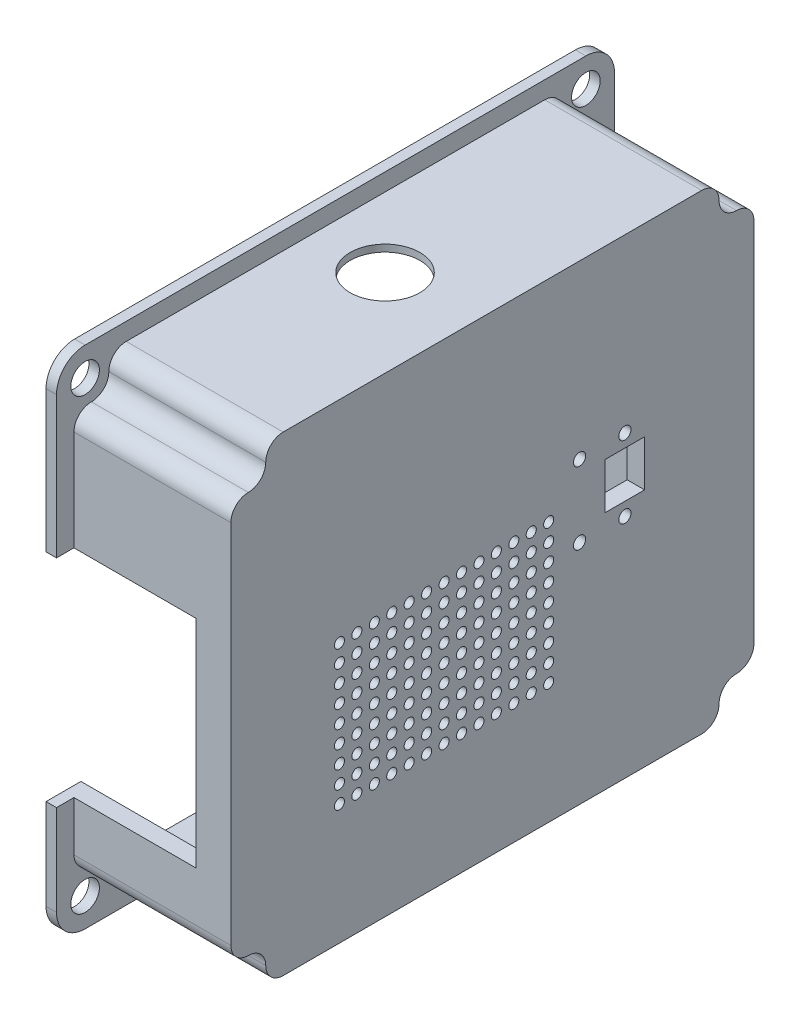
SolidWorks part; units mm, degrees
ref_plane "Alzado" through (0, 0, 0) normal (1, 0, 0) x (0, 1, 0)
ref_plane "Planta" through (0, 0, 0) normal (0, 0, 1) x (0, 1, 0)
ref_plane "Vista lateral" through (0, 0, 0) normal (0, 1, 0) x (-1, 0, 0)
sketch "Croquis2" plane through (0, 0, 0) normal (1, 0, 0) x (0, 1, 0)
  line L0 (72.5, 80) -> (57.5, 80) construction
  line L3 (-64.3, 80) -> (64.3, 80)
  line L4 (72.5, -71.8) -> (72.5, 71.8)
  line L6 (-72.5, 80) -> (-72.5, 65) construction
  line L11 (72.5, 80) -> (72.5, 65) construction
  line L12 (57.5, 75) -> (57.5, 65)
  line L13 (57.5, 65) -> (67.5, 65)
  line L14 (0, 0) -> (0, 80) construction
  line L15 (67.5, 65) -> (67.5, -65)
  line L16 (0, 0) -> (72.5, 0) construction
  line L17 (-57.5, 75) -> (57.5, 75)
  line L18 (-72.5, 80) -> (-57.5, 80) construction
  line L19 (-67.5, 65) -> (-67.5, -65)
  line L21 (-57.5, 65) -> (-67.5, 65)
  line L22 (-57.5, 75) -> (-57.5, 65)
  line L23 (-72.5, -71.8) -> (-72.5, 71.8)
  line L24 (-72.5, -80) -> (-57.5, -80) construction
  line L25 (-72.5, -80) -> (-72.5, -65) construction
  line L26 (-57.5, -75) -> (-57.5, -65)
  line L27 (-57.5, -65) -> (-67.5, -65)
  line L28 (-57.5, -75) -> (57.5, -75)
  line L29 (-64.3, -80) -> (64.3, -80)
  line L30 (72.5, -80) -> (72.5, -65) construction
  line L31 (72.5, -80) -> (57.5, -80) construction
  line L32 (57.5, -65) -> (67.5, -65)
  line L33 (57.5, -75) -> (57.5, -65)
  arc A2 (64.3, 80) -> (72.5, 71.8) centre (64.3, 71.8) cw
  arc A10 (-64.3, 80) -> (-72.5, 71.8) centre (-64.3, 71.8) ccw
  arc A11 (-64.3, -80) -> (-72.5, -71.8) centre (-64.3, -71.8) cw
  arc A14 (64.3, -80) -> (72.5, -71.8) centre (64.3, -71.8) ccw
  point P4 (0, 75)
  point P21 (-65, 80)
  point P22 (-72.5, 72.5)
  point P30 (72.5, 72.5)
  point P35 (65, 80)
  point P36 (-72.5, 0)
  point P37 (-67.5, 0)
  point P51 (-72.5, -72.5)
  point P52 (-65, -80)
  point P53 (0, -75)
  point P62 (67.5, 0)
  point P63 (65, -80)
  point P64 (72.5, -72.5)
  dimension "D3" = 8.2
  dimension "D4" = 5
  dimension "D2" = 80
  dimension "D10" = 72.5
  dimension "D12" = 15
  dimension "D13" = 15
  dimension "D14" = 5
extrude "Saliente-Extruir1" add sketch "Croquis2" along normal blind 3
sketch "Croquis3" plane through (3, 0, 0) normal (1, 0, 0) x (0, 1, 0)
  line L0 (-57.5, -65) -> (-57.5, -75) construction
  line L1 (-57.5, -75) -> (57.5, -75) construction
  line L2 (57.5, -75) -> (57.5, -65) construction
  line L3 (57.5, -65) -> (67.5, -65) construction
  line L4 (67.5, -65) -> (67.5, 65) construction
  line L5 (67.5, 65) -> (57.5, 65) construction
  line L6 (57.5, 65) -> (57.5, 75) construction
  line L7 (-67.5, -65) -> (-57.5, -65) construction
  line L8 (-67.5, 65) -> (-67.5, -65) construction
  line L9 (57.5, 75) -> (-57.5, 75) construction
  line L10 (-57.5, 75) -> (-57.5, 65) construction
  line L11 (-57.5, 65) -> (-67.5, 65) construction
  line L12 (-57.5, -65) -> (-57.5, -75)
  line L13 (-57.5, -75) -> (57.5, -75)
  line L14 (57.5, -75) -> (57.5, -65)
  line L15 (57.5, -65) -> (67.5, -65)
  line L16 (67.5, -65) -> (67.5, 65)
  line L17 (67.5, 65) -> (57.5, 65)
  line L18 (57.5, 65) -> (57.5, 75)
  line L19 (-67.5, -65) -> (-57.5, -65)
  line L20 (-67.5, 65) -> (-67.5, -65)
  line L21 (57.5, 75) -> (-57.5, 75)
  line L22 (-57.5, 75) -> (-57.5, 65)
  line L23 (-57.5, 65) -> (-67.5, 65)
  line L24 (-52.5, -60) -> (-52.5, -70)
  line L25 (-52.5, -70) -> (52.5, -70)
  line L26 (52.5, -70) -> (52.5, -60)
  line L27 (52.5, -60) -> (62.5, -60)
  line L28 (62.5, -60) -> (62.5, 60)
  line L29 (62.5, 60) -> (52.5, 60)
  line L30 (52.5, 60) -> (52.5, 70)
  line L31 (-62.5, -60) -> (-52.5, -60)
  line L32 (-62.5, 60) -> (-62.5, -60)
  line L33 (52.5, 70) -> (-52.5, 70)
  line L34 (-52.5, 70) -> (-52.5, 60)
  line L35 (-52.5, 60) -> (-62.5, 60)
  dimension "D1" = 5
  dimension "D2" = 5
  dimension "D3" = 5
  dimension "D4" = 5
  dimension "D5" = 5
  dimension "D6" = 5
  dimension "D7" = 5
  dimension "D8" = 5
  dimension "D9" = 5
  dimension "D10" = 5
  dimension "D11" = 5
  dimension "D12" = 5
extrude "Saliente-Extruir2" add sketch "Croquis3" along normal blind 40 and the other way up to surface (3 mm away) other way up to face at (0, 0, 0)
sketch "Croquis4" plane through (3, 0, 0) normal (1, 0, 0) x (0, 1, 0)
  circle A0 centre (64.3, -71.8) radius 4.1 construction
  circle A1 centre (64.3, 71.8) radius 4.1 construction
  circle A2 centre (-64.3, 71.8) radius 4.1 construction
  circle A3 centre (-64.3, -71.8) radius 4.1 construction
  circle A12 centre (64.3, -71.8) radius 4.1
  circle A13 centre (64.3, 71.8) radius 4.1
  circle A14 centre (-64.3, 71.8) radius 4.1
  circle A15 centre (-64.3, -71.8) radius 4.1
extrude "Cortar-Extruir1" cut sketch "Croquis4" against normal blind 10
fillet "Redondeo1" radius 5 24 edges at (23, 57.5, 75) (23, 57.5, 65) (23, 67.5, 65) (21.5, -52.5, -60) (21.5, -52.5, -70) (21.5, 52.5, -70) (21.5, 52.5, -60) (21.5, 62.5, -60) (21.5, -52.5, 70) (21.5, -52.5, 60) (21.5, -62.5, 60) (21.5, -62.5, -60) (23, -67.5, -65) (23, -67.5, 65) (23, -57.5, 65) (23, 67.5, -65) (23, 57.5, -65) (23, 57.5, -75) (23, -57.5, -75) (23, -57.5, -65) (23, -57.5, 75) (21.5, 52.5, 70) (21.5, 62.5, 60) (21.5, 52.5, 60)
sketch "Croquis5" plane through (43, 0, 0) normal (1, 0, 0) x (0, 1, 0)
  line L4 (-67.5, 60) -> (-67.5, -60)
  line L5 (-52.5, -75) -> (52.5, -75)
  line L6 (67.5, -60) -> (67.5, 60)
  line L7 (52.5, 75) -> (-52.5, 75)
  line L8 (-67.5, 60) -> (-67.5, -60)
  line L9 (-52.5, -75) -> (52.5, -75)
  line L10 (67.5, -60) -> (67.5, 60)
  line L11 (52.5, 75) -> (-52.5, 75)
  circle A0 centre (7.0733, -16.1362) radius 1.45
  circle A1 centre (2.0733, -16.1362) radius 1.45
  circle A2 centre (-2.9267, -16.1362) radius 1.45
  circle A3 centre (-7.9267, -16.1362) radius 1.45
  circle A4 centre (-12.9267, -16.1362) radius 1.45
  circle A5 centre (-17.9267, -16.1362) radius 1.45
  circle A6 centre (-22.9267, -16.1362) radius 1.45
  circle A7 centre (-27.9267, -16.1362) radius 1.45
  circle A8 centre (-32.9267, -16.1362) radius 1.45
  circle A9 centre (2.0733, -11.1362) radius 1.45
  circle A10 centre (-2.9267, -11.1362) radius 1.45
  circle A11 centre (-7.9267, -11.1362) radius 1.45
  arc A12 (-67.5, -60) -> (-62.5, -65) centre (-62.5, -60) ccw
  arc A13 (-57.5, -70) -> (-62.5, -65) centre (-62.5, -70) ccw
  arc A14 (-57.5, -70) -> (-52.5, -75) centre (-52.5, -70) ccw
  arc A15 (52.5, -75) -> (57.5, -70) centre (52.5, -70) ccw
  arc A16 (62.5, -65) -> (57.5, -70) centre (62.5, -70) ccw
  arc A17 (62.5, -65) -> (67.5, -60) centre (62.5, -60) ccw
  arc A18 (67.5, 60) -> (62.5, 65) centre (62.5, 60) ccw
  arc A19 (57.5, 70) -> (62.5, 65) centre (62.5, 70) ccw
  arc A20 (57.5, 70) -> (52.5, 75) centre (52.5, 70) ccw
  arc A21 (-52.5, 75) -> (-57.5, 70) centre (-52.5, 70) ccw
  arc A22 (-62.5, 65) -> (-57.5, 70) centre (-62.5, 70) ccw
  arc A23 (-62.5, 65) -> (-67.5, 60) centre (-62.5, 60) ccw
  arc A24 (-67.5, -60) -> (-62.5, -65) centre (-62.5, -60) ccw
  arc A25 (-57.5, -70) -> (-62.5, -65) centre (-62.5, -70) ccw
  arc A26 (-57.5, -70) -> (-52.5, -75) centre (-52.5, -70) ccw
  arc A27 (52.5, -75) -> (57.5, -70) centre (52.5, -70) ccw
  arc A28 (62.5, -65) -> (57.5, -70) centre (62.5, -70) ccw
  arc A29 (62.5, -65) -> (67.5, -60) centre (62.5, -60) ccw
  arc A30 (67.5, 60) -> (62.5, 65) centre (62.5, 60) ccw
  arc A31 (57.5, 70) -> (62.5, 65) centre (62.5, 70) ccw
  arc A32 (57.5, 70) -> (52.5, 75) centre (52.5, 70) ccw
  arc A33 (-52.5, 75) -> (-57.5, 70) centre (-52.5, 70) ccw
  arc A34 (-62.5, 65) -> (-57.5, 70) centre (-62.5, 70) ccw
  arc A35 (-62.5, 65) -> (-67.5, 60) centre (-62.5, 60) ccw
  circle A36 centre (-12.9267, -11.1362) radius 1.45
  circle A37 centre (-17.9267, -11.1362) radius 1.45
  circle A38 centre (-22.9267, -11.1362) radius 1.45
  circle A39 centre (-27.9267, -11.1362) radius 1.45
  circle A40 centre (-32.9267, -11.1362) radius 1.45
  circle A41 centre (2.0733, -6.1362) radius 1.45
  circle A42 centre (-2.9267, -6.1362) radius 1.45
  circle A43 centre (-7.9267, -6.1362) radius 1.45
  circle A44 centre (-12.9267, -6.1362) radius 1.45
  circle A45 centre (-17.9267, -6.1362) radius 1.45
  circle A46 centre (-22.9267, -6.1362) radius 1.45
  circle A47 centre (-27.9267, -6.1362) radius 1.45
  circle A48 centre (-32.9267, -6.1362) radius 1.45
  circle A49 centre (2.0733, -1.1362) radius 1.45
  circle A50 centre (-2.9267, -1.1362) radius 1.45
  circle A51 centre (-7.9267, -1.1362) radius 1.45
  circle A52 centre (-12.9267, -1.1362) radius 1.45
  circle A53 centre (-17.9267, -1.1362) radius 1.45
  circle A54 centre (-22.9267, -1.1362) radius 1.45
  circle A55 centre (-27.9267, -1.1362) radius 1.45
  circle A56 centre (-32.9267, -1.1362) radius 1.45
  circle A57 centre (2.0733, 3.8638) radius 1.45
  circle A58 centre (-2.9267, 3.8638) radius 1.45
  circle A59 centre (-7.9267, 3.8638) radius 1.45
  circle A60 centre (-12.9267, 3.8638) radius 1.45
  circle A61 centre (-17.9267, 3.8638) radius 1.45
  circle A62 centre (-22.9267, 3.8638) radius 1.45
  circle A63 centre (-27.9267, 3.8638) radius 1.45
  circle A64 centre (-32.9267, 3.8638) radius 1.45
  circle A65 centre (2.0733, 8.8638) radius 1.45
  circle A66 centre (-2.9267, 8.8638) radius 1.45
  circle A67 centre (-7.9267, 8.8638) radius 1.45
  circle A68 centre (-12.9267, 8.8638) radius 1.45
  circle A69 centre (-17.9267, 8.8638) radius 1.45
  circle A70 centre (-22.9267, 8.8638) radius 1.45
  circle A71 centre (-27.9267, 8.8638) radius 1.45
  circle A72 centre (-32.9267, 8.8638) radius 1.45
  circle A73 centre (2.0733, 13.8638) radius 1.45
  circle A74 centre (-2.9267, 13.8638) radius 1.45
  circle A75 centre (-7.9267, 13.8638) radius 1.45
  circle A76 centre (-12.9267, 13.8638) radius 1.45
  circle A77 centre (-17.9267, 13.8638) radius 1.45
  circle A78 centre (-22.9267, 13.8638) radius 1.45
  circle A79 centre (-27.9267, 13.8638) radius 1.45
  circle A80 centre (-32.9267, 13.8638) radius 1.45
  circle A81 centre (2.0733, 18.8638) radius 1.45
  circle A82 centre (-2.9267, 18.8638) radius 1.45
  circle A83 centre (-7.9267, 18.8638) radius 1.45
  circle A84 centre (-12.9267, 18.8638) radius 1.45
  circle A85 centre (-17.9267, 18.8638) radius 1.45
  circle A86 centre (-22.9267, 18.8638) radius 1.45
  circle A87 centre (-27.9267, 18.8638) radius 1.45
  circle A88 centre (-32.9267, 18.8638) radius 1.45
  circle A89 centre (2.0733, 23.8638) radius 1.45
  circle A90 centre (-2.9267, 23.8638) radius 1.45
  circle A91 centre (-7.9267, 23.8638) radius 1.45
  circle A92 centre (-12.9267, 23.8638) radius 1.45
  circle A93 centre (-17.9267, 23.8638) radius 1.45
  circle A94 centre (-22.9267, 23.8638) radius 1.45
  circle A95 centre (-27.9267, 23.8638) radius 1.45
  circle A96 centre (-32.9267, 23.8638) radius 1.45
  circle A97 centre (2.0733, 28.8638) radius 1.45
  circle A98 centre (-2.9267, 28.8638) radius 1.45
  circle A99 centre (-7.9267, 28.8638) radius 1.45
  circle A100 centre (-12.9267, 28.8638) radius 1.45
  circle A101 centre (-17.9267, 28.8638) radius 1.45
  circle A102 centre (-22.9267, 28.8638) radius 1.45
  circle A103 centre (-27.9267, 28.8638) radius 1.45
  circle A104 centre (-32.9267, 28.8638) radius 1.45
  circle A105 centre (2.0733, 33.8638) radius 1.45
  circle A106 centre (-2.9267, 33.8638) radius 1.45
  circle A107 centre (-7.9267, 33.8638) radius 1.45
  circle A108 centre (-12.9267, 33.8638) radius 1.45
  circle A109 centre (-17.9267, 33.8638) radius 1.45
  circle A110 centre (-22.9267, 33.8638) radius 1.45
  circle A111 centre (-27.9267, 33.8638) radius 1.45
  circle A112 centre (-32.9267, 33.8638) radius 1.45
  circle A113 centre (2.0733, 38.8638) radius 1.45
  circle A114 centre (-2.9267, 38.8638) radius 1.45
  circle A115 centre (-7.9267, 38.8638) radius 1.45
  circle A116 centre (-12.9267, 38.8638) radius 1.45
  circle A117 centre (-17.9267, 38.8638) radius 1.45
  circle A118 centre (-22.9267, 38.8638) radius 1.45
  circle A119 centre (-27.9267, 38.8638) radius 1.45
  circle A120 centre (-32.9267, 38.8638) radius 1.45
  circle A121 centre (2.0733, 43.8638) radius 1.45
  circle A122 centre (-2.9267, 43.8638) radius 1.45
  circle A123 centre (-7.9267, 43.8638) radius 1.45
  circle A124 centre (-12.9267, 43.8638) radius 1.45
  circle A125 centre (-17.9267, 43.8638) radius 1.45
  circle A126 centre (-22.9267, 43.8638) radius 1.45
  circle A127 centre (-27.9267, 43.8638) radius 1.45
  circle A128 centre (-32.9267, 43.8638) radius 1.45
  circle A129 centre (7.0733, -11.1362) radius 1.45
  circle A130 centre (7.0733, -6.1362) radius 1.45
  circle A131 centre (7.0733, -1.1362) radius 1.45
  circle A132 centre (7.0733, 3.8638) radius 1.45
  circle A133 centre (7.0733, 8.8638) radius 1.45
  circle A134 centre (7.0733, 13.8638) radius 1.45
  circle A135 centre (7.0733, 18.8638) radius 1.45
  circle A136 centre (7.0733, 23.8638) radius 1.45
  circle A137 centre (7.0733, 28.8638) radius 1.45
  circle A138 centre (7.0733, 33.8638) radius 1.45
  circle A139 centre (7.0733, 38.8638) radius 1.45
  circle A140 centre (7.0733, 43.8638) radius 1.45
  dimension "D1" = 0
  dimension "D2" = 9
  dimension "D3" = 13
extrude "Saliente-Extruir3" add sketch "Croquis5" along normal blind 5
sketch "Croquis6" plane through (0, 0, 75) normal (0, 0, 1) x (1, 0, 0)
  line L0 (0, -64.3) -> (0, 64.3) construction
  line L1 (0, 23.7304) -> (38, 23.7304)
  line L2 (0, 23.7304) -> (0, -38.2696)
  line L3 (0, -38.2696) -> (38, -38.2696)
  line L4 (38, 23.7304) -> (38, -38.2696)
  dimension "D1" = 62
  dimension "D2" = 38
extrude "Cortar-Extruir2" cut sketch "Croquis6" against normal blind 7 and the other way blind 7
sketch "Croquis7" plane through (0, 67.5, 0) normal (0, 1, 0) x (-1, 0, 0)
  line L0 (-43, 5.7963) -> (-3, 5.7963) construction
  line L1 (-43, -55) -> (-43, 55) construction
  line L2 (-3, -71.8) -> (-3, 71.8) construction
  circle A0 centre (-23, 5.7963) radius 10
  dimension "D1" = 20
extrude "Cortar-Extruir3" cut sketch "Croquis7" against normal up to surface (135 mm away) up to face at (25.5, -67.5, 0)
sketch "Croquis8" plane through (0, 62.5, 0) normal (0, -1, 0) x (1, 0, 0)
  circle A0 centre (23, 5.7963) radius 14
  point P3 (23, 27.7533)
  dimension "D1" = 28
extrude "Cortar-Extruir4" cut sketch "Croquis8" against normal blind 3
fillet "Redondeo2" radius 2 1 edges at (23, 62.5, -8.2037)
sketch "Croquis9" plane through (0, -62.5, 0) normal (0, 1, 0) x (-1, 0, 0)
  circle A0 centre (-23, 5.7963) radius 14
  dimension "D1" = 28
extrude "Cortar-Extruir5" cut sketch "Croquis9" against normal blind 3
fillet "Redondeo3" radius 2 1 edges at (23, -62.5, 19.7963)
sketch "Croquis10" plane through (48, 0, 0) normal (1, 0, 0) x (0, 1, 0)
  line L0 (13.5176, -42.6365) -> (13.5176, -33.2625) construction
  line L1 (1.3176, -32.2625) -> (14.5176, -32.2625)
  line L2 (1.3176, -32.2625) -> (1.3176, -43.6365)
  line L3 (1.3176, -43.6365) -> (14.5176, -43.6365)
  line L4 (14.5176, -32.2625) -> (14.5176, -43.6365)
  line L5 (13.5176, -33.2625) -> (2.3176, -33.2625) construction
  line L6 (2.3176, -42.6365) -> (13.5176, -42.6365) construction
  line L7 (2.3176, -33.2625) -> (2.3176, -42.6365) construction
  circle A0 centre (18.2676, -24.9865) radius 1.75
  circle A1 centre (-2.4324, -24.9865) radius 1.75
  circle A2 centre (-2.4324, -37.9865) radius 1.75
  circle A3 centre (18.2676, -37.9865) radius 1.75
  dimension "D1" = 3.5
  dimension "D4" = 1
  dimension "D5" = 1
  dimension "D6" = 1
  dimension "D7" = 1
  dimension "D2" = 2
  dimension "D3" = 2
extrude "Cortar-Extruir6" cut sketch "Croquis10" against normal blind 10
